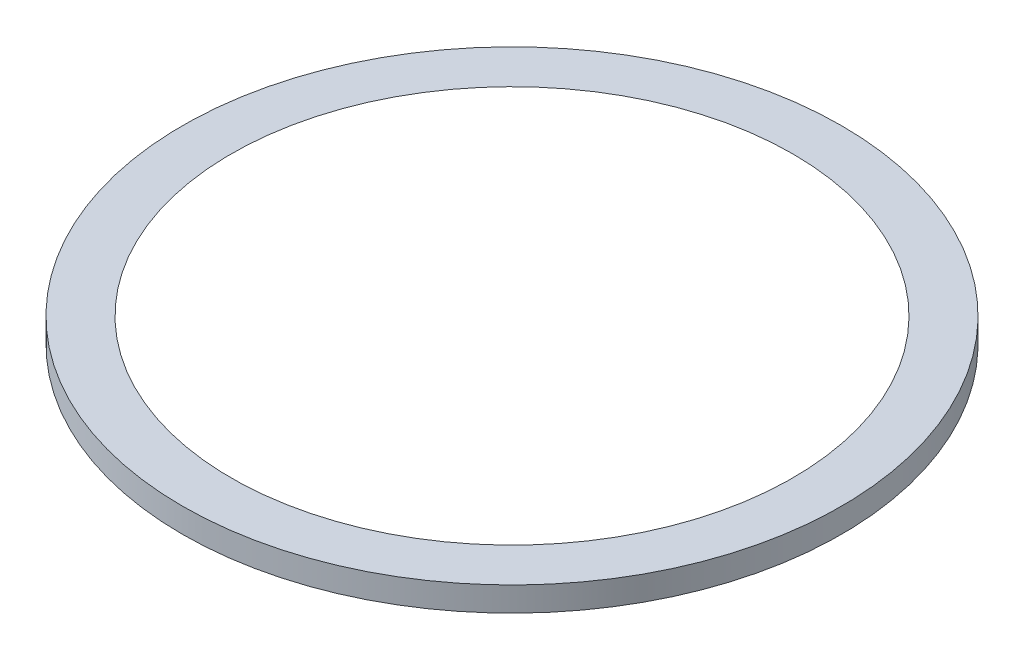
SolidWorks part; units mm, degrees
material "6061 Alloy"
ref_plane "Front Plane" through (0, 0, 0) normal (0, 0, 1) x (1, 0, 0)
ref_plane "Top Plane" through (0, 0, 0) normal (0, 1, 0) x (1, 0, 0)
ref_plane "Right Plane" through (0, 0, 0) normal (1, 0, 0) x (0, 0, -1)
sketch "Sketch1" plane through (0, 0, 0) normal (0, 1, 0) x (1, 0, 0)
  circle A0 centre (0, 0) radius 13.5
  circle A1 centre (0, 0) radius 11.5
  dimension "D1" = 27
  dimension "D2" = 2
extrude "Boss-Extrude1" add sketch "Sketch1" along normal blind 1
sketch "Sketch2" plane through (0, 0, 0) normal (1, 0, 0) x (0, 0, -1)
  line L0 (-11.5, 1) -> (-13.2934, 0)
  line L1 (13.5, 1) -> (-13.5, 1) construction
  line L2 (11.5, 1) -> (-11.5, 1) construction
  line L3 (-13.5, 0) -> (13.5, 0) construction
  line L4 (-13.2934, 0) -> (-11.5, 0)
  line L5 (-11.5, 0) -> (11.5, 0) construction
  line L6 (-11.5, 0) -> (-11.5, 1)
  line L7 (0, -2.0608) -> (0, 5.8713) construction
  point P8 (0, 0)
  point P12 (0, 0)
  dimension "D1" = 2.0534
  dimension "D2" = 11.5
revolve "Cut-Revolve1" cut sketch "Sketch2" angle 360 about L7
